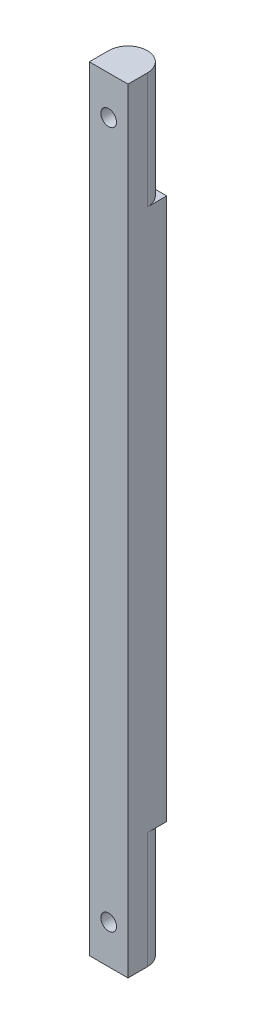
SolidWorks part; units mm, degrees
material "6061-T6 (SS)"
ref_plane "Front Plane" through (0, 0, 0) normal (0, 0, 1) x (1, 0, 0)
ref_plane "Top Plane" through (0, 0, 0) normal (0, 1, 0) x (1, 0, 0)
ref_plane "Right Plane" through (0, 0, 0) normal (1, 0, 0) x (0, 0, -1)
sketch "Sketch1" plane through (0, 0, 0) normal (0, 1, 0) x (1, 0, 0)
  line L0 (-3.175, 3.175) -> (-3.175, 0)
  line L1 (-3.175, 0) -> (3.175, 0)
  line L2 (3.175, 0) -> (3.175, 3.175)
  arc A0 (-3.175, 3.175) -> (3.175, 3.175) centre (0, 3.175) cw
  point P5 (0, 0)
  point P8 (0, 6.35)
  dimension "D2" = 3.175
  dimension "D1" = 6.35
  dimension "D3" = 6.35
extrude "Boss-Extrude1" add sketch "Sketch1" along normal mid plane 127
hole_wizard "#5-40 Tapped Hole1" positions "Sketch2" profile "Sketch3" tap size "#5-40" standard "ANSI Inch" end condition through all
sketch "Sketch2" plane through (0, 0, 0) normal (0, 0, 1) x (1, 0, 0)
  line L0 (-3.175, -63.5) -> (3.175, -63.5) construction
  point P2 (0, -57.15)
  dimension "D1" = 6.35
sketch "Sketch3" plane through (0, -57.15, 0) normal (1, 0, 0) x (0, -1, 0)
  line L0 (0, 0) -> (0, 6.35)
  line L1 (0, 6.35) -> (1.289, 6.35)
  line L2 (1.289, 6.35) -> (1.289, 0)
  line L5 (1.289, 0) -> (0, 0)
  line L11 (0, -6.35) -> (0, 107.95) construction
  dimension "Thru Tap Drill Dia." = 2.5781
  dimension "Thru Tap Drill Depth" = 6.35
cosmetic thread "Hole Thread1" parameters "D2"=3.175
mirror "Mirror1" about plane through (0, 0, 0) normal (0, 1, 0) of "#5-40 Tapped Hole1"
cosmetic thread "Hole Thread2" parameters "D2"=3.175
sketch "Sketch4" plane through (0, -63.5, 0) normal (0, -1, 0) x (1, 0, 0)
  line L0 (-3.175, 0) -> (3.175, 0) construction
  line L1 (3.175, 0) -> (-3.175, 0)
  line L2 (3.175, 0) -> (3.175, -6.35)
  line L3 (3.175, -6.35) -> (-3.175, -6.35)
  line L4 (-3.175, 0) -> (-3.175, -6.35)
  line L5 (3.175, 0) -> (-3.175, -6.35) construction
  line L6 (3.175, -6.35) -> (-3.175, 0) construction
  line L7 (-3.175, -3.175) -> (-3.175, 0) construction
  line L8 (3.175, 0) -> (3.175, -3.175) construction
  point P0 (0, -3.175)
extrude "Boss-Extrude2" add sketch "Sketch4" against normal offset from surface (88.9 mm away) 19.05 from offset 19.05 up to face at (0, 63.5, -2.3813) offset against normal yes
